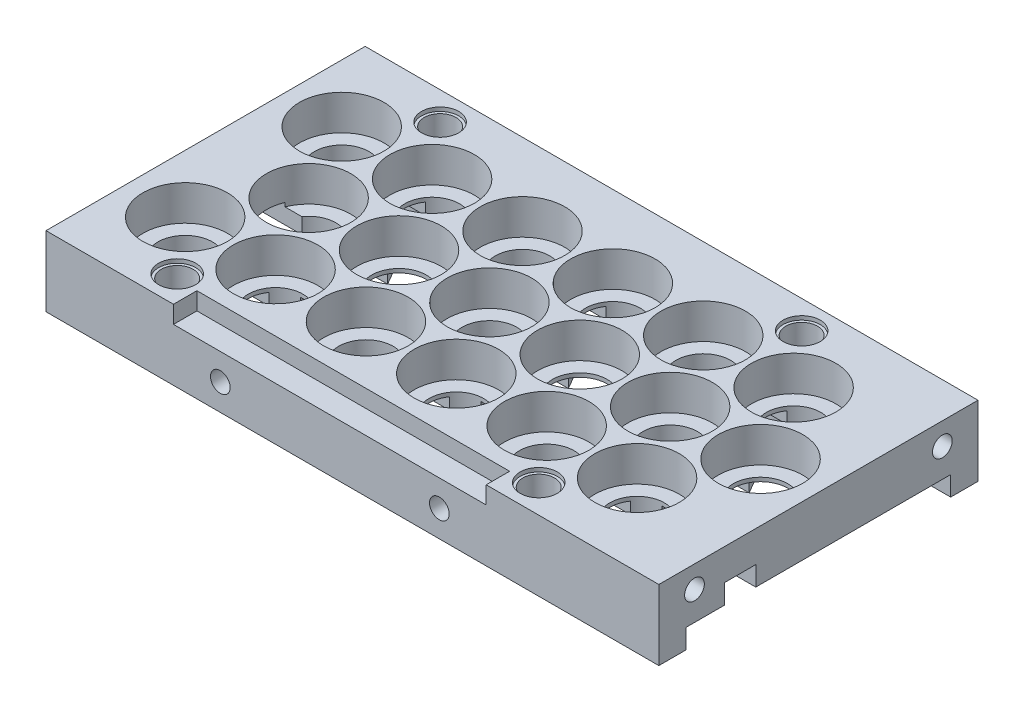
SolidWorks part; units mm, degrees
ref_plane "Front Plane" through (0, 0, 0) normal (0, 0, 1) x (1, 0, 0)
ref_plane "Top Plane" through (0, 0, 0) normal (0, 1, 0) x (1, 0, 0)
ref_plane "Right Plane" through (0, 0, 0) normal (1, 0, 0) x (0, 0, -1)
sketch "Sketch1" plane through (0, 0, 0) normal (0, 1, 0) x (1, 0, 0)
  line L0 (0, 0) -> (11.575, -20.0485) construction
  line L1 (11.575, -20.0485) -> (0, -40.097) construction
  line L2 (0, 0) -> (11.575, 0) construction
  line L3 (11.575, 0) -> (11.575, -20.0485) construction
  line L4 (11.575, -20.0485) -> (11.575, -40.097) construction
  line L5 (11.575, -40.097) -> (0, -40.097) construction
  line L6 (0, 0) -> (23.15, 0) construction
  line L7 (0, 0) -> (23.15, 0) construction
  line L8 (-14.825, -60.922) -> (142.15, -60.922)
  line L9 (-14.825, -60.922) -> (-14.825, 20.825)
  line L10 (-14.825, 20.825) -> (142.15, 20.825)
  line L11 (142.15, -60.922) -> (142.15, 20.825)
  circle A0 centre (0, 0) radius 10.825
  circle A1 centre (11.575, -20.0485) radius 10.825
  circle A2 centre (0, -40.097) radius 10.825
  circle A3 centre (23.15, 0) radius 10.825
  circle A4 centre (34.725, -20.0485) radius 10.825
  circle A5 centre (23.15, -40.097) radius 10.825
  circle A6 centre (46.3, 0) radius 10.825
  circle A7 centre (57.875, -20.0485) radius 10.825
  circle A8 centre (46.3, -40.097) radius 10.825
  circle A9 centre (69.45, 0) radius 10.825
  circle A10 centre (81.025, -20.0485) radius 10.825
  circle A11 centre (69.45, -40.097) radius 10.825
  circle A12 centre (92.6, 0) radius 10.825
  circle A13 centre (104.175, -20.0485) radius 10.825
  circle A14 centre (92.6, -40.097) radius 10.825
  circle A15 centre (115.75, 0) radius 10.825
  circle A16 centre (127.325, -20.0485) radius 10.825
  circle A17 centre (115.75, -40.097) radius 10.825
  circle A18 centre (0, 0) radius 7
  circle A19 centre (11.575, -20.0485) radius 7
  circle A20 centre (0, -40.097) radius 7
  circle A21 centre (23.15, 0) radius 7
  circle A22 centre (34.725, -20.0485) radius 7
  circle A23 centre (23.15, -40.097) radius 7
  circle A24 centre (46.3, 0) radius 7
  circle A25 centre (57.875, -20.0485) radius 7
  circle A26 centre (46.3, -40.097) radius 7
  circle A27 centre (69.45, 0) radius 7
  circle A28 centre (81.025, -20.0485) radius 7
  circle A29 centre (69.45, -40.097) radius 7
  circle A30 centre (92.6, 0) radius 7
  circle A31 centre (104.175, -20.0485) radius 7
  circle A32 centre (92.6, -40.097) radius 7
  circle A33 centre (115.75, 0) radius 7
  circle A34 centre (127.325, -20.0485) radius 7
  circle A35 centre (115.75, -40.097) radius 7
  dimension "D3" = 21.65
  dimension "D11" = 14
  dimension "D1" = 60
  dimension "D2" = 60
  dimension "D4" = 1.5
  dimension "D6" = 23.15
  dimension "D7" = 4
  dimension "D8" = 4
  dimension "D9" = 10
  dimension "D10" = 10
  dimension "D13" = 23.15
  dimension "D5" = 6
  dimension "D12" = 6
extrude "Boss-Extrude2" add sketch "Sketch1" along normal blind 11 and the other way blind 2 contours L8 L11 L10 L9 A17 A16 A15 A14 A13 A12 A11 A10 A9 A8 A7 A6 A5 A4 A3 A2 A1 A0 region at (-13.0551, 0, 20.0485)
extrude "Boss-Extrude3" add sketch "Sketch1<3>" along normal blind 2 and the other way blind 2 contours A0 A18 | A3 A21 | A6 A24 | A9 A27 | A12 A30 | A15 A33 | A1 A19 | A4 A22 | A7 A25 | A10 A28 | A13 A31 | A16 A34 | A17 A35 | A14 A32 | A11 A29 | A8 A26 | A5 A23 | A2 A20 region at (-10.5188, 0, 0) region at (1.0562, 0, 20.0485) region at (-10.5188, 0, 40.097) region at (12.6312, 0, 0) region at (24.2062, 0, 20.0485) region at (12.6312, 0, 40.097) region at (35.7812, 0, 0) region at (47.3562, 0, 20.0485) region at (35.7812, 0, 40.097) region at (58.9312, 0, 0) region at (70.5062, 0, 20.0485) region at (58.9312, 0, 40.097) region at (82.0812, 0, 0) region at (93.6562, 0, 20.0485) region at (82.0812, 0, 40.097) region at (105.2312, 0, 0) region at (116.8062, 0, 20.0485) region at (105.2312, 0, 40.097)
sketch "Sketch1<3>" plane through (0, 0, 0) normal (0, 1, 0) x (1, 0, 0) same geometry as "Sketch1"
sketch "Sketch9" plane through (0, 11, 0) normal (0, 1, 0) x (1, 0, 0)
  line L0 (11.575, -60.922) -> (11.575, 20.825)
  line L1 (-14.825, 20.825) -> (142.15, 20.825) construction
  line L2 (104.175, 20.825) -> (104.175, -60.922)
  line L3 (-14.825, -60.922) -> (142.15, -60.922) construction
  circle A0 centre (11.575, 13.625) radius 4.0767
  circle A1 centre (11.575, -53.722) radius 4.0767
  circle A2 centre (104.175, -53.722) radius 4.0767
  circle A3 centre (104.175, 13.625) radius 4.0767
  point P0 (11.575, 13.625)
  point P7 (11.575, -20.0485)
  point P15 (104.175, -20.0485)
  point P20 (104.175, 13.625)
  point P21 (104.175, -53.722)
  point P22 (11.575, -53.722)
  dimension "D5" = 8.1534
  dimension "D1" = 7.2
  dimension "D4" = 7.2
extrude "Cut-Extrude3" cut sketch "Sketch9" against normal up to next contours A2 | A1 | A0 | A3
sketch "Sketch10" plane through (0, 11, 0) normal (0, 1, 0) x (1, 0, 0)
  circle A0 centre (11.575, 13.625) radius 4.7625
  circle A1 centre (104.175, 13.625) radius 4.7625
  circle A2 centre (104.175, -53.722) radius 4.7625
  circle A3 centre (11.575, -53.722) radius 4.7625
  dimension "D1" = 9.525
extrude "Cut-Extrude4" cut sketch "Sketch10" against normal blind 1
sketch "Sketch13" plane through (0, -2, 0) normal (0, -1, 0) x (1, 0, 0)
  line L0 (142.15, 60.922) -> (142.15, -20.825) construction
  line L5 (3.575, 53.722) -> (3.575, 60.922)
  line L8 (-14.825, 60.922) -> (142.15, 60.922) construction
  line L9 (3.575, 60.922) -> (19.575, 60.922)
  line L10 (19.575, 60.922) -> (19.575, 53.722)
  line L12 (57.875, 20.0485) -> (57.875, -20.825) construction
  line L13 (-14.825, -20.825) -> (142.15, -20.825) construction
  line L14 (11.575, 20.0485) -> (127.325, 20.0485) construction
  line L16 (96.175, 60.922) -> (96.175, 53.722)
  line L17 (112.175, 60.922) -> (96.175, 60.922)
  line L18 (112.175, 53.722) -> (112.175, 60.922)
  line L19 (-14.825, 60.922) -> (142.15, 60.922)
  line L20 (-14.825, 60.922) -> (-14.825, 53.922)
  line L21 (-14.825, 53.922) -> (142.15, 53.922)
  line L22 (142.15, 60.922) -> (142.15, 53.922)
  line L23 (142.15, -20.825) -> (142.15, -13.825)
  line L24 (-14.825, -13.825) -> (142.15, -13.825)
  line L25 (-14.825, -20.825) -> (-14.825, -13.825)
  line L26 (-14.825, -20.825) -> (142.15, -20.825)
  line L27 (112.175, -13.625) -> (112.175, -20.825)
  line L28 (112.175, -20.825) -> (96.175, -20.825)
  line L29 (96.175, -20.825) -> (96.175, -13.625)
  line L32 (19.575, -20.825) -> (19.575, -13.625)
  line L33 (3.575, -20.825) -> (19.575, -20.825)
  line L34 (3.575, -13.625) -> (3.575, -20.825)
  circle A4 centre (11.575, 53.722) radius 6.5
  circle A5 centre (11.575, 53.722) radius 8
  circle A6 centre (104.175, 53.722) radius 8
  circle A7 centre (104.175, 53.722) radius 6.5
  circle A8 centre (104.175, -13.625) radius 6.5
  circle A9 centre (104.175, -13.625) radius 8
  circle A10 centre (11.575, -13.625) radius 8
  circle A11 centre (11.575, -13.625) radius 6.5
  line M15 (142.15, 60.922) -> (-14.825, 60.922)
  line M16 (-14.825, 60.922) -> (-14.825, -20.825)
  line M17 (-14.825, -20.825) -> (142.15, -20.825)
  line M18 (142.15, -20.825) -> (142.15, 60.922)
  dimension "D1" = 13
  dimension "D2" = 16
  dimension "D3" = 7
extrude "Boss-Extrude7" add sketch "Sketch13" along normal blind 5 contours L21 L5 M16 M15 | A5 L5 L21 M15 | A5 L21 L10 M15 | L10 L21 L16 M15 | L21 A5 L19 A4 | A5 L21 A4 | L21 A6 L16 M15 | L21 A7 A6 L19 | L21 A7 A6 | A6 L21 L18 M15 | L18 L21 M18 M15 | A9 L24 L29 L26 | L28 A9 L24 A8 | A9 L26 L27 L24 | L24 L27 L26 M18 | L32 L26 L29 L24 | L24 A9 A8 | L34 L24 M16 M17 | L26 A10 L24 L34 | L24 A11 A10 | L24 A11 A10 L33 | L24 A10 L26 L32 region at (3.7554, -2, 53.8197) region at (-5.625, -2, 57.422) region at (4.8234, -2, 59.2386) region at (4.9969, -2, 57.9605) region at (18.3266, -2, 59.2386) region at (57.875, -2, 57.422) region at (-5.625, -2, -17.325) region at (97.4234, -2, 59.2386) region at (4.8234, -2, -19.1416) region at (96.3554, -2, 53.8197) region at (97.5969, -2, 57.9605) region at (3.7554, -2, -13.7228) region at (4.3278, -2, -13.9996) region at (110.9266, -2, 59.2386) region at (127.1625, -2, 57.422) region at (18.3266, -2, -19.1416) region at (57.875, -2, -17.325) region at (97.4234, -2, -19.1416) region at (127.1625, -2, -17.325) region at (96.3554, -2, -13.7228) region at (96.9278, -2, -13.9996) region at (110.9266, -2, -19.1416)
sketch "Sketch2" plane through (0, -2, 0) normal (0, -1, 0) x (1, 0, 0)
  line L0 (0, 40.097) -> (11.575, 20.0485) construction
  line L1 (3.4641, 42.097) -> (15.0391, 22.0485)
  line L2 (-3.4641, 38.097) -> (8.1109, 18.0485)
  line L3 (11.575, 20.0485) -> (0, 0) construction
  line L4 (15.0391, 18.0485) -> (3.4641, -2)
  line L5 (8.1109, 22.0485) -> (-3.4641, 2)
  line L6 (19.6859, 38.097) -> (31.2609, 18.0485)
  line L7 (26.6141, 42.097) -> (38.1891, 22.0485)
  line L8 (31.2609, 22.0485) -> (19.6859, 2)
  line L9 (38.1891, 18.0485) -> (26.6141, -2)
  line L10 (23.15, 40.097) -> (34.725, 20.0485) construction
  line L11 (34.725, 20.0485) -> (23.15, 0) construction
  line L12 (42.8359, 38.097) -> (54.4109, 18.0485)
  line L13 (49.7641, 42.097) -> (61.3391, 22.0485)
  line L14 (54.4109, 22.0485) -> (42.8359, 2)
  line L15 (61.3391, 18.0485) -> (49.7641, -2)
  line L16 (46.3, 40.097) -> (57.875, 20.0485) construction
  line L17 (57.875, 20.0485) -> (46.3, 0) construction
  line L18 (65.9859, 38.097) -> (77.5609, 18.0485)
  line L19 (72.9141, 42.097) -> (84.4891, 22.0485)
  line L20 (77.5609, 22.0485) -> (65.9859, 2)
  line L21 (84.4891, 18.0485) -> (72.9141, -2)
  line L22 (69.45, 40.097) -> (81.025, 20.0485) construction
  line L23 (81.025, 20.0485) -> (69.45, 0) construction
  line L24 (89.1359, 38.097) -> (100.7109, 18.0485)
  line L25 (96.0641, 42.097) -> (107.6391, 22.0485)
  line L26 (100.7109, 22.0485) -> (89.1359, 2)
  line L27 (107.6391, 18.0485) -> (96.0641, -2)
  line L28 (92.6, 40.097) -> (104.175, 20.0485) construction
  line L29 (104.175, 20.0485) -> (92.6, 0) construction
  line L30 (112.2859, 38.097) -> (123.8609, 18.0485)
  line L31 (119.2141, 42.097) -> (130.7891, 22.0485)
  line L32 (123.8609, 22.0485) -> (112.2859, 2)
  line L33 (130.7891, 18.0485) -> (119.2141, -2)
  line L34 (115.75, 40.097) -> (127.325, 20.0485) construction
  line L35 (127.325, 20.0485) -> (115.75, 0) construction
  line L36 (-3.4641, 38.097) -> (19.6859, 38.097) construction
  line L37 (0, 40.097) -> (115.75, 40.097) construction
  line L38 (0, 44.097) -> (115.75, 44.097)
  line L39 (0, 36.097) -> (115.75, 36.097)
  line L40 (11.575, 20.0485) -> (127.325, 20.0485) construction
  line L41 (11.575, 24.0485) -> (127.325, 24.0485)
  line L42 (11.575, 16.0485) -> (127.325, 16.0485)
  line L43 (0, 0) -> (115.75, 0) construction
  line L44 (0, 4) -> (115.75, 4)
  line L45 (0, -4) -> (115.75, -4)
  arc A0 (3.4641, 42.097) -> (-3.4641, 38.097) centre (0, 40.097) ccw
  arc A1 (8.1109, 18.0485) -> (15.0391, 22.0485) centre (11.575, 20.0485) ccw
  arc A2 (15.0391, 18.0485) -> (8.1109, 22.0485) centre (11.575, 20.0485) ccw
  arc A3 (-3.4641, 2) -> (3.4641, -2) centre (0, 0) ccw
  arc A4 (26.6141, 42.097) -> (19.6859, 38.097) centre (23.15, 40.097) ccw
  arc A5 (31.2609, 18.0485) -> (38.1891, 22.0485) centre (34.725, 20.0485) ccw
  arc A6 (38.1891, 18.0485) -> (31.2609, 22.0485) centre (34.725, 20.0485) ccw
  arc A7 (19.6859, 2) -> (26.6141, -2) centre (23.15, 0) ccw
  arc A8 (49.7641, 42.097) -> (42.8359, 38.097) centre (46.3, 40.097) ccw
  arc A9 (54.4109, 18.0485) -> (61.3391, 22.0485) centre (57.875, 20.0485) ccw
  arc A10 (61.3391, 18.0485) -> (54.4109, 22.0485) centre (57.875, 20.0485) ccw
  arc A11 (42.8359, 2) -> (49.7641, -2) centre (46.3, 0) ccw
  arc A12 (72.9141, 42.097) -> (65.9859, 38.097) centre (69.45, 40.097) ccw
  arc A13 (77.5609, 18.0485) -> (84.4891, 22.0485) centre (81.025, 20.0485) ccw
  arc A14 (84.4891, 18.0485) -> (77.5609, 22.0485) centre (81.025, 20.0485) ccw
  arc A15 (65.9859, 2) -> (72.9141, -2) centre (69.45, 0) ccw
  arc A16 (96.0641, 42.097) -> (89.1359, 38.097) centre (92.6, 40.097) ccw
  arc A17 (100.7109, 18.0485) -> (107.6391, 22.0485) centre (104.175, 20.0485) ccw
  arc A18 (107.6391, 18.0485) -> (100.7109, 22.0485) centre (104.175, 20.0485) ccw
  arc A19 (89.1359, 2) -> (96.0641, -2) centre (92.6, 0) ccw
  arc A20 (119.2141, 42.097) -> (112.2859, 38.097) centre (115.75, 40.097) ccw
  arc A21 (123.8609, 18.0485) -> (130.7891, 22.0485) centre (127.325, 20.0485) ccw
  arc A22 (130.7891, 18.0485) -> (123.8609, 22.0485) centre (127.325, 20.0485) ccw
  arc A23 (112.2859, 2) -> (119.2141, -2) centre (115.75, 0) ccw
  arc A24 (0, 44.097) -> (0, 36.097) centre (0, 40.097) ccw
  arc A25 (115.75, 36.097) -> (115.75, 44.097) centre (115.75, 40.097) ccw
  arc A26 (11.575, 24.0485) -> (11.575, 16.0485) centre (11.575, 20.0485) ccw
  arc A27 (127.325, 16.0485) -> (127.325, 24.0485) centre (127.325, 20.0485) ccw
  arc A28 (0, 4) -> (0, -4) centre (0, 0) ccw
  arc A29 (115.75, -4) -> (115.75, 4) centre (115.75, 0) ccw
  point P3 (5.7875, 30.0727)
  point P8 (5.7875, 10.0242)
  point P18 (28.9375, 30.0727)
  point P25 (28.9375, 10.0242)
  point P34 (52.0875, 30.0727)
  point P39 (52.0875, 10.0242)
  point P48 (75.2375, 30.0727)
  point P53 (75.2375, 10.0242)
  point P62 (98.3875, 30.0727)
  point P67 (98.3875, 10.0242)
  point P76 (121.5375, 30.0727)
  point P81 (121.5375, 10.0242)
  point P91 (57.875, 40.097)
  point P96 (69.45, 20.0485)
  point P103 (57.875, 0)
  dimension "D1" = 8
  dimension "D3" = 23.15
  dimension "D4" = 8
  dimension "D5" = 8
  dimension "D6" = 8
extrude "Cut-Extrude1" cut sketch "Sketch2" against normal blind 3 contours L1 L39 L38 | L42 L8 L6 L41 | L13 L39 L38 | L18 L41 L19 L39 | L25 L39 L38 | L42 L32 L30 L41 | L42 L20 L18 L41 | L45 L44 L4 | L45 L44 L15 | L45 L44 L27 | L44 L21 L42 L20 | L39 L13 | L39 L25 | L39 L19 | L41 L6 | L44 L4 | L44 L15 | L44 L21 | L44 L27 | L41 L30 | L32 L42 | L41 L18 | L20 L42 | L44 L9 L42 L8 | L8 L42 | L39 L7 | L39 L1 | A23 L32 L44 L45 | L30 L41 L31 | L42 L32 L33 | L6 L41 L7 L39 | A7 L9 L44 L8 region at (12.1489, -2, 40.3471) region at (0.784, -2, 39.6443) region at (21.9471, -2, 20.0485) region at (28.9375, -2, 30.0727) region at (23.8945, -2, 39.601) region at (30.3235, -2, 22.793) region at (58.4489, -2, 40.3471) region at (47.0445, -2, 39.601) region at (30.3235, -2, 17.304) region at (70.1945, -2, 39.601) region at (0.784, -2, 0.4527) region at (28.9375, -2, 10.0242) region at (104.7489, -2, 40.3471) region at (93.3445, -2, 39.601) region at (12.1489, -2, -0.2501) region at (23.8945, -2, 0.496) region at (68.2471, -2, 20.0485) region at (75.2375, -2, 30.0727) region at (76.6235, -2, 22.793) region at (121.4671, -2, 30.6948) region at (58.4489, -2, -0.2501) region at (47.0445, -2, 0.496) region at (76.6235, -2, 17.304) region at (114.5471, -2, 20.0485) region at (70.1945, -2, 0.496) region at (75.2375, -2, 10.0242) region at (121.4671, -2, 9.4022) region at (122.9235, -2, 22.793) region at (104.7489, -2, -0.2501) region at (93.3445, -2, 0.496) region at (122.9235, -2, 17.304)
sketch "Sketch19" plane through (0, 0, 60.922) normal (0, 0, 1) x (1, 0, 0)
  line L0 (11.575, 11) -> (104.175, 11)
  line L1 (-14.825, 11) -> (142.15, 11) construction
  line L2 (97.925, 11) -> (17.825, 11)
  line L3 (17.825, 11) -> (97.925, 11)
  line L4 (17.825, 11) -> (17.825, 6.525)
  line L5 (97.925, 11) -> (97.925, 6.525)
  line L6 (17.825, 6.525) -> (97.925, 6.525)
  point P5 (57.875, 11)
  point P9 (57.875, 11)
  dimension "D1" = 92.6
  dimension "D2" = 26.4
  dimension "D3" = 80.1
  dimension "D4" = 4.475
extrude "Cut-Extrude6" cut sketch "Sketch19" against normal blind 6 contours L4 L6 L5 L0 region at (57.875, 8.7625, 60.922)
sketch "Sketch20" plane through (0, 0, 60.922) normal (0, 0, 1) x (1, 0, 0)
  line L0 (29.825, 6.525) -> (85.925, 6.525)
  line L1 (29.825, 6.525) -> (29.825, -0.2375)
  line L2 (85.925, 6.525) -> (85.925, -0.2375)
  line L3 (29.825, -0.2375) -> (85.925, -0.2375)
  line L4 (29.825, 6.525) -> (17.825, 6.525) construction
  line L5 (85.925, 6.525) -> (97.925, 6.525) construction
  line L6 (57.875, 6.525) -> (57.875, -7)
  line L9 (142.15, -7) -> (-14.825, -7) construction
  circle A0 centre (29.825, -0.2375) radius 2.525
  circle A1 centre (85.925, -0.2375) radius 2.525
  point P9 (57.875, -0.2375)
  dimension "D2" = 5.05
  dimension "D1" = 12
extrude "Cut-Extrude7" cut sketch "Sketch20" against normal blind 6.604 contours L1 A0 L3 | L3 A0 L1 | L3 A1 L2 | L2 A1 L3 region at (30.8966, 0.8341, 60.922) region at (29.4678, -0.5947, 60.922) region at (86.2822, -0.5947, 60.922) region at (84.8534, 0.8341, 60.922)
sketch "Sketch22" plane through (142.15, 0, 0) normal (1, 0, 0) x (0, 0, -1)
  line L5 (-60.922, 11) -> (20.825, 11) construction
  circle A0 centre (-51.7985, 5.325) radius 2.525
  circle A1 centre (-51.7985, 5.325) radius 2.525
  circle A2 centre (11.7015, 5.325) radius 2.525
  circle A3 centre (-51.7985, 5.325) radius 2.159 construction
  circle A4 centre (11.7015, 5.325) radius 2.159 construction
  point P5 (-20.0485, 11)
  dimension "D1" = 5.05
  dimension "D2" = 0
extrude "Cut-Extrude8" cut sketch "Sketch22" against normal blind 6.604 contours A0 | A0 | A1 | A1 | A2 region at (142.15, 5.325, 51.7985) region at (142.15, 5.325, -11.7015)
sketch "Sketch26" plane through (0, -2, 0) normal (0, -1, 0) x (1, 0, 0)
  line L0 (57.875, -13.825) -> (57.875, -4) construction
  line L1 (132.15, -8.9125) -> (57.875, -8.9125) construction
  line L2 (57.875, -8.9125) -> (-10.825, -8.9125) construction
  line L3 (11.575, 20.0485) -> (82.7573, 20.0485)
  line L4 (57.875, 49.0095) -> (-10.825, 49.0095) construction
  line L5 (132.15, 49.0095) -> (57.875, 49.0095) construction
  line L6 (57.875, 53.922) -> (57.875, 44.097) construction
  line L7 (19.5725, 53.922) -> (96.1775, 53.922) construction
  line L8 (52.0446, 44.097) -> (63.7054, 44.097) construction
  line L9 (-14.825, 53.922) -> (-14.825, -13.825) construction
  line L10 (142.15, 53.922) -> (142.15, -13.825) construction
  circle A0 centre (132.15, -8.9125) radius 1.9431
  circle A1 centre (57.875, -8.9125) radius 1.9431
  circle A2 centre (-10.825, -8.9125) radius 1.9431
  circle A3 centre (-10.825, 49.0095) radius 1.9431
  circle A4 centre (57.875, 49.0095) radius 1.9431
  circle A5 centre (132.15, 49.0095) radius 1.9431
  dimension "D1" = 3.8862
  dimension "D2" = 4
  dimension "D3" = 10
extrude "Cut-Extrude9" cut sketch "Sketch26" against normal blind 5 contours A3 | A4 | A5 | A2 | A1 | A0
sketch "Sketch27" plane through (0, -2, 0) normal (0, -1, 0) x (1, 0, 0)
  line L0 (11.575, 20.0485) -> (-14.825, 20.0485) construction
  line L1 (11.575, 16.0485) -> (-14.825, 16.0485)
  line L2 (11.575, 24.0485) -> (-14.825, 24.0485)
  line L3 (-14.825, 53.922) -> (-14.825, -13.825) construction
  line L4 (115.75, 40.097) -> (142.15, 40.097) construction
  line L6 (115.75, 44.097) -> (142.15, 44.097)
  line L7 (115.75, 36.097) -> (142.15, 36.097)
  line L8 (142.15, 53.922) -> (142.15, -13.825) construction
  arc A0 (11.575, 16.0485) -> (11.575, 24.0485) centre (11.575, 20.0485) ccw
  arc A1 (-14.825, 24.0485) -> (-14.825, 16.0485) centre (-14.825, 20.0485) ccw
  arc A2 (115.75, 44.097) -> (115.75, 36.097) centre (115.75, 40.097) ccw
  arc A3 (142.15, 36.097) -> (142.15, 44.097) centre (142.15, 40.097) ccw
  point P3 (-1.625, 20.0485)
  point P8 (128.95, 40.097)
  point P14 (132.271, 13.3812)
  point P15 (115.75, 40.097)
  point P20 (142.15, 40.097)
  dimension "D1" = 8
  dimension "D2" = 8
extrude "Cut-Extrude10" cut sketch "Sketch27" against normal blind 5
sketch "Sketch28" plane through (0, 3, 0) normal (0, -1, 0) x (1, 0, 0)
  line L0 (-3.25, 24.0485) -> (-3.25, 16.0485) construction
  line L1 (1.5161, 24.0485) -> (-14.825, 24.0485) construction
  line L2 (-14.825, 16.0485) -> (1.5161, 16.0485) construction
  line L3 (-10.825, 24.0485) -> (-10.825, 16.0485) construction
  line L4 (-10.825, 20.0485) -> (-3.25, 20.0485) construction
  line L5 (-14.825, 24.0485) -> (-14.825, 16.0485) construction
  line L7 (-3.25, 20.0485) -> (0.75, 20.0485) construction
  line L8 (138.15, 44.097) -> (138.15, 36.097) construction
  line L9 (130.575, 44.097) -> (130.575, 36.097) construction
  line L10 (130.575, 40.097) -> (138.15, 40.097) construction
  line L11 (138.15, 40.097) -> (142.15, 40.097) construction
  line L12 (142.15, 44.097) -> (125.8089, 44.097) construction
  line L13 (125.8089, 36.097) -> (142.15, 36.097) construction
  line L14 (142.15, 44.097) -> (142.15, 36.097) construction
  line L15 (130.575, 40.097) -> (126.575, 40.097) construction
  circle A0 centre (-3.25, 20.0485) radius 1.9431
  circle A1 centre (-10.825, 20.0485) radius 1.9431
  arc A2 (1.5161, 24.0485) -> (1.5161, 16.0485) centre (11.575, 20.0485) ccw construction
  circle A3 centre (138.15, 40.097) radius 1.9431
  circle A4 centre (130.575, 40.097) radius 1.9431
  arc A5 (125.8089, 36.097) -> (125.8089, 44.097) centre (115.75, 40.097) ccw construction
  dimension "D1" = 3.8862
  dimension "D6" = 3.8862
  dimension "D2" = 4
  dimension "D3" = 4
  dimension "D4" = 4
  dimension "D5" = 4
extrude "Cut-Extrude11" cut sketch "Sketch28" against normal blind 5
equation "\"hole_diameter\"= 21.65"
equation "\"D3@Sketch1\"=\"hole_diameter\""
equation "\"cell_spacing\"= 1.5"
equation "\"D4@Sketch1\"=\"cell_spacing\""
equation "\"D6@Sketch1\"=\"hole_diameter\"+\"cell_spacing\""
equation "\"len_spacing\"= 4"
equation "\"D7@Sketch1\"=\"len_spacing\""
equation "\"D8@Sketch1\"=\"len_spacing\""
equation "\"wid_spacing\"= 10"
equation "\"D9@Sketch1\"=\"wid_spacing\""
equation "\"D10@Sketch1\"=\"wid_spacing\""
equation "\"nipple\"= 14"
equation "\"D11@Sketch1\"=\"nipple\""
equation "\"D13@Sketch1\"=\"hole_diameter\"+\"cell_spacing\""
equation "\"channel\"= 8"
equation "\"D1@Sketch2\"=\"channel\""
equation "\"D3@Sketch2\"=\"hole_diameter\"+\"cell_spacing\""
equation "\"D4@Sketch2\"=\"channel\""
equation "\"D5@Sketch2\"=\"channel\""
equation "\"D6@Sketch2\"=\"channel\""
equation "\"lip\"= 7"
equation "\"lip_height\"= 1"
equation "\"outer_fillet\"=6"
equation "\"insert_placement\"= 7.2"
equation "\"D4@Sketch9\"=\"insert_placement\""
equation "\"D1@Sketch9\"=\"insert_placement\""
equation "\"heat_insert_diameter\"=8.1534"
equation "\"D5@Sketch9\"=\"heat_insert_diameter\""
equation "\"heat_insert_lip_diameter\"=9.525"
equation "\"D1@Sketch10\"=\"heat_insert_lip_diameter\""
equation "\"bolt_head_diameter\"=13"
equation "\"D1@Sketch13\"=\"bolt_head_diameter\""
equation "\"D2@Sketch13\"=\"bolt_head_diameter\"+3"
equation "\"D3@Sketch13\"=\"lip\""
equation "\"small_heat_insert\"= .153in"
equation "\"bdm_cut_depth\"=6"
equation "\"D1@Cut-Extrude6\"=\"bdm_cut_depth\""
equation "\"D1@Cut-Extrude7\"=\"heat_insert_depth\""
equation "\"D2@Sketch20\"=\"heat_6_32\""
equation "\"heat_insert_depth\"= .26in"
equation "\"D1@Cut-Extrude8\"=\"heat_insert_depth\""
equation "\"D1@Sketch26\"=\"small_heat_insert\""
equation "\"D1@Sketch27\"=\"channel\""
equation "\"D2@Sketch27\"=\"channel\""
equation "\"D1@Sketch28\"=\"small_heat_insert\""
equation "\"D6@Sketch28\"=\"small_heat_insert\""
equation "\"heat_6_32\"=5.05"
equation "\"D1@Sketch22\"=\"heat_6_32\""
equation "\"heat_insert_space\"=6"
equation "\"heat_insert\"=5.5"
